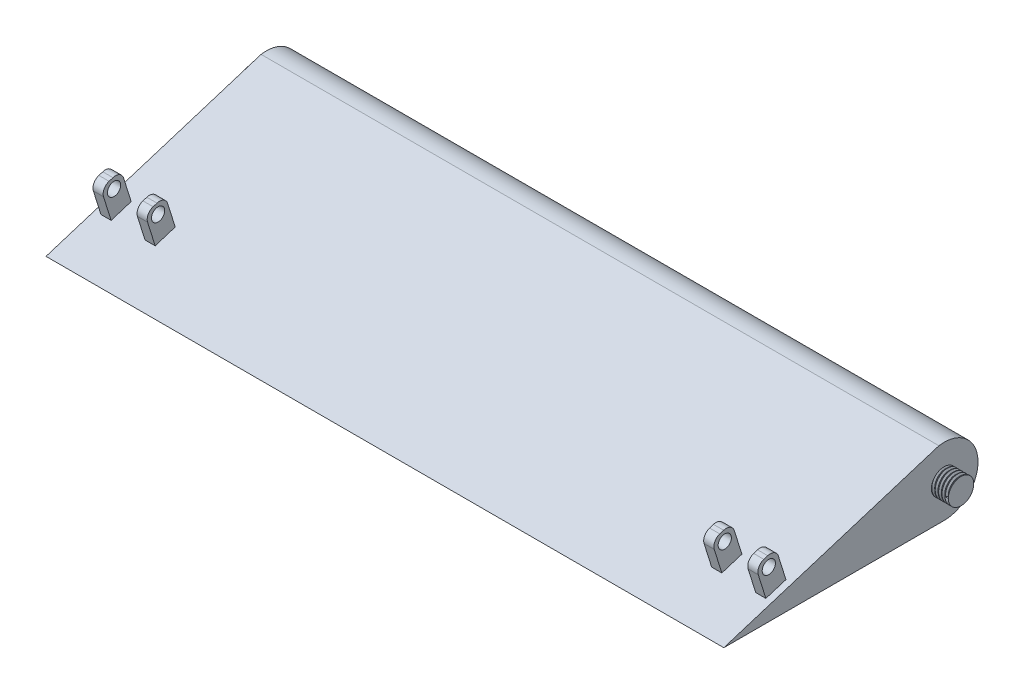
SolidWorks part; units mm, degrees
material "PET"
ref_plane "Front Plane" through (0, 0, 0) normal (0, 0, 1) x (1, 0, 0)
ref_plane "Top Plane" through (0, 0, 0) normal (0, 1, 0) x (1, 0, 0)
ref_plane "Right Plane" through (0, 0, 0) normal (1, 0, 0) x (0, 0, -1)
sketch "Sketch2" plane through (0, 0, 0) normal (1, 0, 0) x (0, 0, -1)
  line L0 (0, -25.4) -> (-165.1, -25.4)
  line L3 (-165.1, -25.4) -> (-3.9077, 25.0976)
  circle A0 centre (0, 0) radius 12.7
  arc A1 (0, -25.4) -> (-3.9077, 25.0976) centre (0, 0) ccw
  dimension "D1" = 165.1
  dimension "D2" = 25.4
  dimension "D3" = 25.4
extrude "Boss-Extrude2" add sketch "Sketch2" along normal blind 508
ref_plane "Plane1" through (254, 0, 0) normal (-1, 0, 0) x (0, 0, 1)
sketch "Sketch3" plane through (254, 0, 0) normal (-1, 0, 0) x (0, 0, 1)
  circle A0 centre (0, 0) radius 12.7
  dimension "D1" = 25.4
extrude "Boss-Extrude3" add sketch "Sketch3" along normal mid plane 508 separate body
sketch "Sketch4" plane through (0, 0, 0) normal (-1, 0, 0) x (0, 0, 1)
  circle A0 centre (0, 0) radius 9.525
  dimension "D1" = 19.05
extrude "Boss-Extrude4" add sketch "Sketch4" along normal blind 12.7
thread "Thread1" pitch 2.54 method cut profile "Thread Profile1" start angle 0, offset 0, length 0, pitch 2.54, diameter 19.05
ref_plane "Plane2" through (-12.7, 0, -9.525) normal (0, -1, 0) x (0, 0, -1)
sketch "Thread Profile1" plane through (-12.7, 0, -9.525) normal (0, -1, 0) x (0, 0, -1)
  line L0 (0, 0) -> (0, 2.54) construction
  line L11 (0, 0) -> (0, 2.2225)
  line L12 (0, 2.2225) -> (-1.3748, 1.4287)
  line L13 (-1.3748, 1.4287) -> (-1.3748, 0.7937)
  line L15 (-1.3748, 0.7937) -> (0, 0)
  line L17 (-1.3748, 1.1112) -> (0, 1.1112) construction
  point P2 (0, 0)
  dimension "Pitch" = 2.54
  dimension "Profile_Angle" = 60
  dimension "Profile_Land" = 0.635
  dimension "Profile_Height" = 1.3748
mirror "Mirror3" about plane through (254, 0, 0) normal (-1, 0, 0) of "Boss-Extrude4"
thread "Thread2" pitch 2.54 method cut profile "Thread Profile2" start angle 0, offset 0, length 0, pitch 2.54, diameter 19.05
ref_plane "Plane3" through (520.7, 0, 9.525) normal (0, -1, 0) x (0, 0, 1)
sketch "Thread Profile2" plane through (520.7, 0, 9.525) normal (0, -1, 0) x (0, 0, 1)
  line L0 (0, 0) -> (0, 2.54) construction
  line L11 (0, 0) -> (0, 2.2225)
  line L12 (0, 2.2225) -> (-1.3748, 1.4287)
  line L13 (-1.3748, 1.4287) -> (-1.3748, 0.7937)
  line L15 (-1.3748, 0.7937) -> (0, 0)
  line L17 (-1.3748, 1.1112) -> (0, 1.1112) construction
  point P2 (0, 0)
  dimension "Pitch" = 2.54
  dimension "Profile_Angle" = 60
  dimension "Profile_Land" = 0.635
  dimension "Profile_Height" = 1.3748
sketch "Sketch10" plane through (0, 23.9694, 7.509) normal (0, 0.9543, 0.2989) x (1, 0, 0)
  line L1 (4.826, -111.2951) -> (12.446, -111.2951)
  line L2 (4.826, -111.2951) -> (4.826, -127.0431)
  line L3 (4.826, -127.0431) -> (12.446, -127.0431)
  line L4 (12.446, -111.2951) -> (12.446, -127.0431)
  line L5 (0, 3.7739) -> (0, -165.1431) construction
  line L6 (508, -165.1431) -> (0, -165.1431) construction
  line L8 (37.846, -111.2951) -> (45.466, -111.2951)
  line L9 (37.846, -111.2951) -> (37.846, -127.0431)
  line L10 (37.846, -127.0431) -> (45.466, -127.0431)
  line L11 (45.466, -111.2951) -> (45.466, -127.0431)
  point P6 (4.826, -119.1691)
  dimension "D1" = 45.974
  dimension "D2" = 7.62
  dimension "D3" = 15.748
  dimension "D4" = 4.826
  dimension "D5" = 25.4
extrude "Boss-Extrude5" add sketch "Sketch10" along normal blind 25.4
fillet "Fillet1" radius 6.35 4 edges at (8.636, 14.9362, 121.3078) (8.636, 10.2284, 136.3357) (41.656, 10.2284, 136.3357) (41.656, 14.9362, 121.3078)
mirror "Mirror4" about plane through (254, 0, 0) normal (-1, 0, 0) of "Fillet1", "Boss-Extrude5"
sketch "Sketch12" plane through (4.826, 0, 0) normal (-1, 0, 0) x (0, 0, 1)
  line L0 (134.4373, 4.1688) -> (128.7423, -14.01) construction
  line L1 (127.3674, 13.0379) -> (130.276, 12.1267) construction
  circle A0 centre (126.5438, 5.3108) radius 4.953
  dimension "D1" = 9.906
  dimension "D2" = 7.874
  dimension "D3" = 7.62
extrude "Cut-Extrude1" cut sketch "Sketch12" against normal through all
